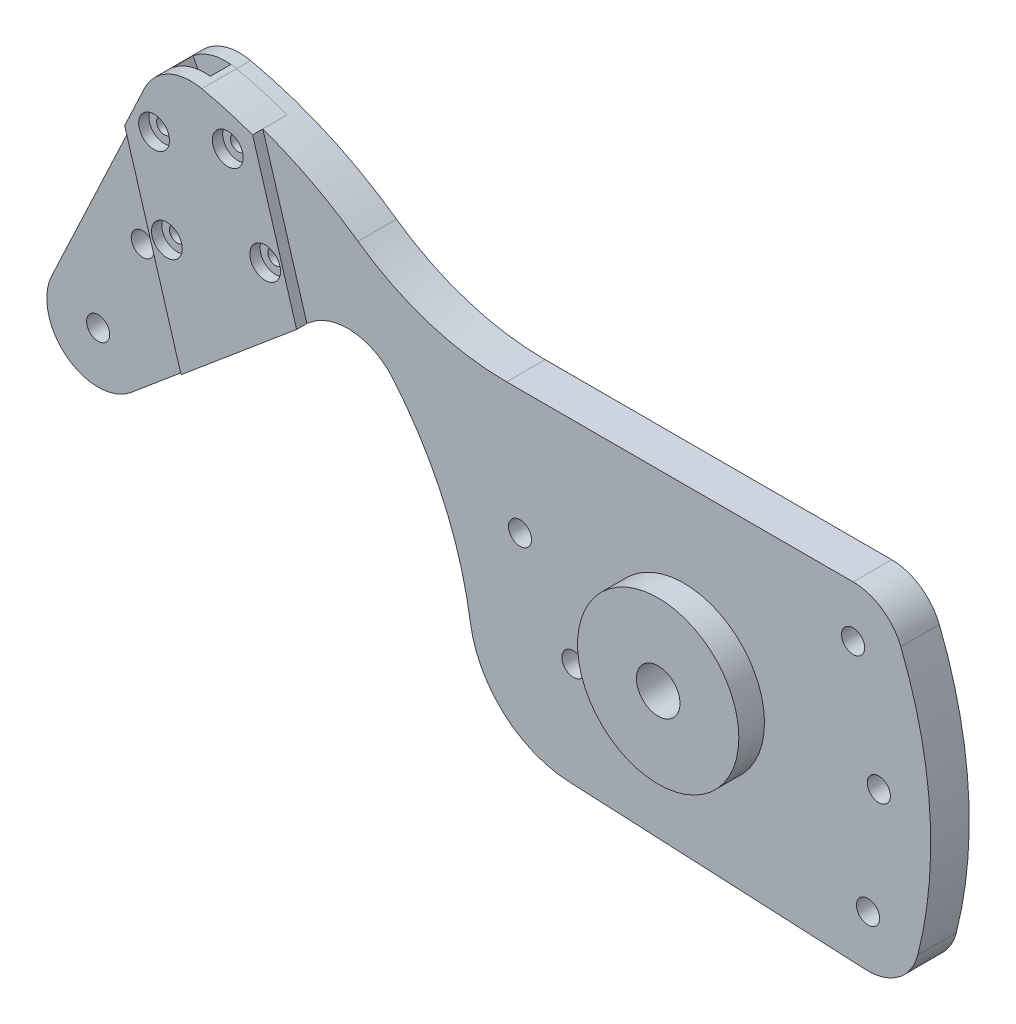
SolidWorks part; units mm, degrees
ref_plane "Front Plane" through (0, 0, 0) normal (0, 0, 1) x (1, 0, 0)
ref_plane "Top Plane" through (0, 0, 0) normal (0, 1, 0) x (1, 0, 0)
ref_plane "Right Plane" through (0, 0, 0) normal (1, 0, 0) x (0, 0, -1)
sketch "Sketch1" plane through (0, 0, 0) normal (0, 0, 1) x (1, 0, 0)
  line L1 (-4.25, -4.25) -> (4.25, -4.25) construction
  line L2 (-4.25, -4.25) -> (-4.25, 4.25) construction
  line L3 (-4.25, 4.25) -> (4.25, 4.25) construction
  line L4 (4.25, -4.25) -> (4.25, 4.25) construction
  line L5 (-4.25, -4.25) -> (4.25, 4.25) construction
  line L6 (-4.25, 4.25) -> (4.25, -4.25) construction
  line L7 (35.3984, -31.7883) -> (-22.5002, -28.984)
  line L9 (-114.4671, 24.4556) -> (-123.1671, 5.9556)
  line L10 (-107.6899, -5.9604) -> (-72.8648, 23.2613)
  line L11 (-114.4671, 24.4556) -> (-103.0859, 48.6569)
  line L16 (-65.4725, 14.4515) -> (-108.3178, -21.5) construction
  line L17 (50.9822, -33.5) -> (-177.2181, -33.5) construction
  line L20 (-34.5382, 32.4) -> (32.9822, 32.4)
  circle A0 centre (0, 0) radius 4.25
  circle A1 centre (-31.9178, 8.2) radius 2.25
  circle A2 centre (-21.5178, -8.7) radius 2.25
  circle A3 centre (32.9822, 22.4) radius 2.25
  circle A4 centre (37.9822, -0.1) radius 2.25
  circle A5 centre (35.8822, -21.8) radius 2.25
  circle A6 centre (35.8822, -21.8) radius 2.25 construction
  circle A7 centre (37.9822, -0.1) radius 2.25 construction
  circle A8 centre (32.9822, 22.4) radius 2.25 construction
  circle A9 centre (-31.9178, 8.2) radius 2.25 construction
  circle A10 centre (-21.5178, -8.7) radius 2.25 construction
  arc A12 (-41.6083, -11.6627) -> (-22.5002, -28.984) centre (-21.5178, -8.7) ccw
  arc A13 (32.5913, -31.6523) -> (28.0429, 32.4) centre (-33.3577, -4.1478) ccw construction
  arc A14 (45.5723, -24.2704) -> (42.2664, 26.1153) centre (-33.3577, -4.1478) ccw
  arc A15 (35.3984, -31.7883) -> (45.5723, -24.2704) centre (35.8822, -21.8) ccw
  arc A16 (42.2664, 26.1153) -> (32.9822, 32.4) centre (32.9822, 22.4) ccw
  circle A17 centre (-105.4178, 20.2) radius 2.25
  circle A18 centre (-33.3577, -4.1478) radius 81.4546 construction
  circle A19 centre (-114.1178, 1.7) radius 2.25
  circle A21 centre (-105.4178, 20.2) radius 2.25 construction
  circle A22 centre (-114.1178, 1.7) radius 2.25 construction
  circle A23 centre (-105.4178, 20.2) radius 10 construction
  arc A24 (-123.1671, 5.9556) -> (-107.6899, -5.9604) centre (-114.1178, 1.7) ccw
  arc A27 (-91.9187, 54.1744) -> (-103.0859, 48.6569) centre (-94.0366, 44.4013) ccw
  circle A31 centre (-33.3577, -4.1478) radius 71.4546 construction
  arc A32 (-41.6083, -11.6627) -> (-56.6627, 21.8438) centre (-108.3178, -21.5) ccw
  arc A33 (-31.0568, -26.628) -> (-91.9187, 54.1744) centre (-108.3178, -21.5) ccw
  arc A34 (-63.487, 41.6328) -> (-34.5382, 32.4) centre (-34.5382, 82.4) ccw
  arc A35 (-56.6627, 21.8438) -> (-72.8648, 23.2613) centre (-65.4725, 14.4515) ccw
  circle A36 centre (-65.4725, 14.4515) radius 10.5004 construction
  circle A37 centre (-108.3178, -21.5) radius 67.4309 construction
  circle A38 centre (-108.3178, -21.5) radius 77.4309 construction
  circle A39 centre (-108.3178, -21.5) radius 10.5004 construction
  circle A40 centre (-108.3178, -21.5) radius 11.5004 construction
  circle A41 centre (0, 0) radius 33 construction
  point P35 (50.3427, -4.5217)
  point P37 (37.1696, 16.7103)
  point P54 (-36.0565, -0.0269)
  point P75 (-40.8381, -1.4887)
  dimension "D1" = 8.5
  dimension "D3" = 10
  dimension "D5" = 50
  dimension "D7" = 40
  dimension "D4" = 10
  dimension "D2" = 10
  dimension "D8" = 1
extrude "Boss-Extrude1" add sketch "Sketch1" along normal mid plane 9.5 contours A0 L4 L3 | A0 L1 L4 | A0 L2 L1 | A0 L3 L2 | A35 A32 A12 A33 A27 L11 L9 A24 L10 A17 A19 region at (4.1562, 2.3635, 0) region at (-82.595, 21.4109, 0)
sketch "Sketch2" plane through (0, 0, 0) normal (0, 0, 1) x (1, 0, 0)
  line L0 (-94.0366, 44.4013) -> (-96.9145, 53.9782) construction
  line L1 (-78.2271, 18.7618) -> (-72.8648, 23.2613)
  line L2 (-94.0366, 44.4013) -> (-84.6999, 13.3304) construction
  line L3 (-92.0846, 44.9879) -> (-78.2271, 18.7618)
  line L4 (-95.0124, 54.3536) -> (-94.0366, 44.4013) construction
  line L5 (-94.0366, 44.4013) -> (-90.5122, 8.4534) construction
  line L6 (-98.7084, 53.2429) -> (-94.0366, 44.4013) construction
  line L7 (-94.0366, 44.4013) -> (-79.7943, 17.4467) construction
  line L8 (-100.3823, 52.1299) -> (-95.9887, 43.8147)
  line L9 (-93.0022, 54.3476) -> (-92.0846, 44.9879)
  line L12 (-92.369, 6.8953) -> (-78.2271, 18.7618)
  line L13 (-107.6899, -5.9604) -> (-72.8648, 23.2613) construction
  line L14 (-101.3327, 53.9285) -> (-91.0539, 34.4751) construction
  line L15 (-93.2007, 56.3721) -> (-91.0539, 34.4751) construction
  line L16 (-95.9887, 43.8147) -> (-92.369, 6.8953)
  line L18 (-97.0194, 54.3274) -> (-78.2271, 18.7618) construction
  line L19 (-97.0194, 54.3274) -> (-92.369, 6.8953) construction
  line L20 (-92.369, 6.8953) -> (-107.6899, -5.9604)
  line L22 (-94.0366, 44.4013) -> (-90.3786, 7.0905) construction
  line L23 (-94.0366, 44.4013) -> (-79.9955, 17.8274) construction
  arc A0 (-93.0022, 54.3476) -> (-100.3823, 52.1299) centre (-94.0366, 44.4013) ccw
  arc A1 (-95.0124, 54.3536) -> (-98.7084, 53.2429) centre (-94.0366, 44.4013) ccw construction
  arc A2 (-93.2007, 56.3721) -> (-101.3327, 53.9285) centre (-94.0366, 44.4013) ccw construction
  arc A3 (-91.9187, 54.1744) -> (-103.0859, 48.6569) centre (-94.0366, 44.4013) ccw construction
  point P33 (-96.9145, 53.9782)
  dimension "D3" = 7
  dimension "D4" = 20
  dimension "D1" = 2
  dimension "D2" = 2
extrude "Cut-Extrude1" cut sketch "Sketch2" against normal mid plane 4 contours A0 L8 L12 L9 region at (-89.8285, 28.8905, 0)
ref_plane "Plane1" through (-20.0256, 66.6414, 0) normal (-0.2878, 0.9577, 0) x (0.9577, 0.2878, 0)
sketch "Sketch4" plane through (0, 0, 4.75) normal (0, 0, 1) x (1, 0, 0)
  line L10 (-101.2193, 42.2429) -> (-86.8539, 46.5597) construction
  line L11 (-17.9186, 67.2745) -> (-22.1325, 66.0083) construction
  line L12 (-98.7212, 25.2426) -> (-79.5673, 30.9983) construction
  line L13 (-94.0366, 44.4013) -> (-89.1443, 28.1205) construction
  line L15 (-92.0846, 44.9879) -> (-93.0022, 54.3476)
  line L16 (-78.2271, 18.7618) -> (-92.0846, 44.9879)
  line L17 (-92.369, 6.8953) -> (-78.2271, 18.7618)
  line L18 (-95.9887, 43.8147) -> (-92.369, 6.8953)
  line L19 (-100.3823, 52.1299) -> (-95.9887, 43.8147)
  line L20 (-92.0846, 44.9879) -> (-93.0022, 54.3476) construction
  line L21 (-78.2271, 18.7618) -> (-92.0846, 44.9879) construction
  line L22 (-92.369, 6.8953) -> (-78.2271, 18.7618) construction
  line L23 (-95.9887, 43.8147) -> (-92.369, 6.8953) construction
  line L24 (-100.3823, 52.1299) -> (-95.9887, 43.8147) construction
  circle A0 centre (-98.7212, 25.2426) radius 1.5
  circle A1 centre (-101.2193, 42.2429) radius 1.5
  circle A2 centre (-86.8539, 46.5597) radius 1.5
  circle A3 centre (-79.5673, 30.9983) radius 1.5
  arc A7 (-93.0022, 54.3476) -> (-100.3823, 52.1299) centre (-94.0366, 44.4013) ccw
  arc A8 (-93.0022, 54.3476) -> (-100.3823, 52.1299) centre (-94.0366, 44.4013) ccw construction
  point P13 (-94.0366, 44.4013)
  dimension "D3" = 3
  dimension "D2" = 17
  dimension "D4" = 15
  dimension "D5" = 20
  dimension "D1" = 0
extrude "Cut-Extrude2" cut sketch "Sketch4" against normal through all
sketch "Sketch5" plane through (0, 0, 4.75) normal (0, 0, 1) x (1, 0, 0)
  circle A49 centre (-101.2193, 42.2429) radius 3
  circle A50 centre (-86.8539, 46.5597) radius 3
  circle A51 centre (-79.5673, 30.9983) radius 3
  circle A52 centre (-98.7212, 25.2426) radius 3
  dimension "D1" = 6
extrude "Cut-Extrude3" cut sketch "Sketch5" against normal blind 2
sketch "Sketch3" plane through (-20.0256, 66.6414, 0) normal (-0.2878, 0.9577, 0) x (0.9577, 0.2878, 0)
  line L0 (-90.7804, 2) -> (-63.7804, 2)
  line L1 (-63.7804, 2) -> (-63.7804, -4.75)
  line L2 (-72.4396, -4.75) -> (-48.8199, -4.75) construction
  line L3 (-90.7804, 2) -> (-90.7804, -4.75)
  line L4 (-116.2426, -4.75) -> (-84.7222, -4.75) construction
  line L11 (-79.3187, 2) -> (-75.2421, 2) construction
  point P3 (-77.2804, 2)
  point P11 (-77.2804, 2)
  dimension "D1" = 27
split "Split3" trim tools "Sketch3" bodies to split 111 resulting bodies 112 113
sketch "Sketch6" plane through (0, 0, 4.75) normal (0, 0, 1) x (1, 0, 0)
  line L6 (-95.9577, 3.8841) -> (-106.9455, 40.4497)
  line L7 (-106.9455, 40.4497) -> (-123.1671, 5.9556)
  line L8 (-107.6899, -5.9604) -> (-95.9577, 3.8841)
  line L9 (-95.9577, 3.8841) -> (-106.9455, 40.4497)
  line L10 (-106.9455, 40.4497) -> (-123.1671, 5.9556)
  line L11 (-107.6899, -5.9604) -> (-95.9577, 3.8841)
  line L17 (-82.0221, 51.3292) -> (-73.4422, 22.7768)
  line L18 (-73.4422, 22.7768) -> (-72.8648, 23.2613)
  line L19 (-22.5002, -28.984) -> (35.3984, -31.7883)
  line L20 (32.9822, 32.4) -> (-34.5382, 32.4)
  line L21 (-82.0221, 51.3292) -> (-73.4422, 22.7768)
  line L22 (-73.4422, 22.7768) -> (-72.8648, 23.2613)
  line L23 (-22.5002, -28.984) -> (35.3984, -31.7883)
  line L24 (32.9822, 32.4) -> (-34.5382, 32.4)
  circle A0 centre (0, 0) radius 15.71
  circle A1 centre (-21.5178, -8.7) radius 7.5 construction
  arc A2 (-123.1671, 5.9556) -> (-107.6899, -5.9604) centre (-114.1178, 1.7) ccw
  arc A3 (-123.1671, 5.9556) -> (-107.6899, -5.9604) centre (-114.1178, 1.7) ccw
  arc A19 (-56.6627, 21.8438) -> (-72.8648, 23.2613) centre (-65.4725, 14.4515) ccw
  arc A20 (-41.6083, -11.6627) -> (-56.6627, 21.8438) centre (-108.3178, -21.5) ccw
  arc A21 (-41.6083, -11.6627) -> (-22.5002, -28.984) centre (-21.5178, -8.7) ccw
  arc A22 (35.3984, -31.7883) -> (45.5723, -24.2704) centre (35.8822, -21.8) ccw
  arc A23 (45.5723, -24.2704) -> (42.2664, 26.1153) centre (-33.3577, -4.1478) ccw
  arc A24 (42.2664, 26.1153) -> (32.9822, 32.4) centre (32.9822, 22.4) ccw
  arc A25 (-63.487, 41.6328) -> (-34.5382, 32.4) centre (-34.5382, 82.4) ccw
  arc A26 (-63.487, 41.6328) -> (-82.0221, 51.3292) centre (-108.3178, -21.5) ccw
  arc A27 (-56.6627, 21.8438) -> (-72.8648, 23.2613) centre (-65.4725, 14.4515) ccw
  arc A28 (-41.6083, -11.6627) -> (-56.6627, 21.8438) centre (-108.3178, -21.5) ccw
  arc A29 (-41.6083, -11.6627) -> (-22.5002, -28.984) centre (-21.5178, -8.7) ccw
  arc A30 (35.3984, -31.7883) -> (45.5723, -24.2704) centre (35.8822, -21.8) ccw
  arc A31 (45.5723, -24.2704) -> (42.2664, 26.1153) centre (-33.3577, -4.1478) ccw
  arc A32 (42.2664, 26.1153) -> (32.9822, 32.4) centre (32.9822, 22.4) ccw
  arc A33 (-63.487, 41.6328) -> (-34.5382, 32.4) centre (-34.5382, 82.4) ccw
  arc A34 (-63.487, 41.6328) -> (-82.0221, 51.3292) centre (-108.3178, -21.5) ccw
  dimension "D3" = 15
  dimension "D1" = 0
  dimension "D2" = 0
extrude "Cut-Extrude4" cut sketch "Sketch6" against normal blind 2
sketch "Sketch7" plane through (0, 0, 4.75) normal (0, 0, 1) x (1, 0, 0)
  circle A2 centre (0, 0) radius 15.71
  circle A3 centre (0, 0) radius 15.71
  circle A5 centre (0, 0) radius 4.25
  circle A6 centre (0, 0) radius 4.25
  dimension "D1" = 0
  dimension "D2" = 0
extrude "Boss-Extrude2" add sketch "Sketch7" along normal blind 3
